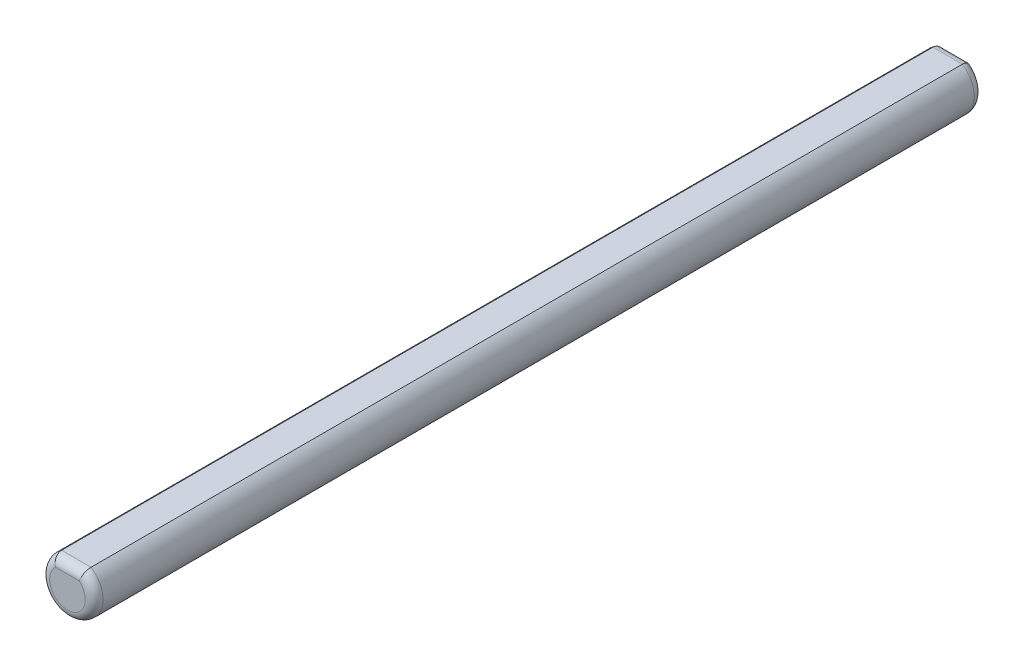
SolidWorks part; units mm, degrees
ref_plane "Front Plane" through (0, 0, 0) normal (0, 0, 1) x (1, 0, 0)
ref_plane "Top Plane" through (0, 0, 0) normal (0, 1, 0) x (1, 0, 0)
ref_plane "Right Plane" through (0, 0, 0) normal (1, 0, 0) x (0, 0, -1)
ref_plane "Plane4" through (0, 0, 115.1204) normal (0, 0, 1) x (1, 0, 0)
sketch "Sketch1" plane through (0, 0, 115.1204) normal (0, 0, 1) x (1, 0, 0)
  line L0 (43.606, 44.3643) -> (40.2894, 44.3643)
  arc A0 (40.2894, 44.3643) -> (43.606, 44.3643) centre (41.9477, 41.8643) ccw
extrude "Boss-Extrude1" add sketch "Sketch1" against normal blind 100
fillet "Fillet1" radius 1 4 edges at (41.9477, 38.8643, 15.1204) (41.9477, 44.3643, 15.1204) (41.9477, 38.8643, 115.1204) (41.9477, 44.3643, 115.1204)
